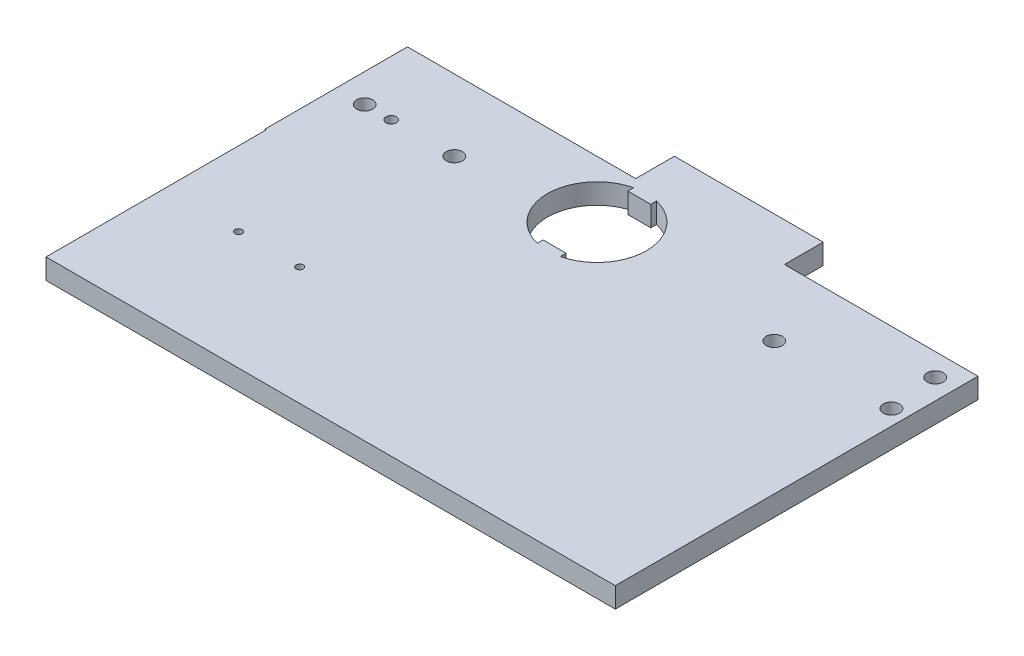
SolidWorks part; units mm, degrees
ref_plane "Front Plane" through (0, 0, 0) normal (0, 0, 1) x (1, 0, 0)
ref_plane "Top Plane" through (0, 0, 0) normal (0, 1, 0) x (1, 0, 0)
ref_plane "Right Plane" through (0, 0, 0) normal (1, 0, 0) x (0, 0, -1)
sketch "Sketch1" plane through (0, 0, 0) normal (0, 1, 0) x (1, 0, 0)
  line L1 (0, 0) -> (280, 0)
  line L2 (0, 0) -> (0, 70)
  line L3 (0, 70) -> (280, 70)
  line L4 (280, 0) -> (280, 70)
  circle A0 centre (14, 35) radius 3.9688
  circle A1 centre (58, 35) radius 3.9688
  circle A2 centre (215, 35) radius 3.9687
  circle A3 centre (272.5, 35) radius 3.9687
  circle A5 centre (270, 59) radius 3.9688
  circle A6 centre (58, 35) radius 27.5336
  circle A7 centre (215, 35) radius 27.5336
  circle A8 centre (27, 35) radius 2.55
  circle A9 centre (215, 35) radius 50.34
  point P20 (0, 0)
  dimension "D3" = 7.9375
  dimension "D6" = 58
  dimension "D7" = 7.9375
  dimension "D9" = 7.9375
  dimension "D12" = 7.5
  dimension "D13" = 7.9375
  dimension "D15" = 7.9375
  dimension "D18" = 55.0672
  dimension "D19" = 55.0672
  dimension "D20" = 5.1
  dimension "D23" = 100.68
  dimension "D1" = 280
  dimension "D2" = 70
  dimension "D4" = 35
  dimension "D5" = 14
  dimension "D8" = 35
  dimension "D10" = 215
  dimension "D11" = 35
  dimension "D14" = 35
  dimension "D16" = 11
  dimension "D17" = 10
  dimension "D21" = 35
  dimension "D22" = 31
extrude "Boss-Extrude7" add sketch "Sketch1" along normal blind 10 contours A9 L3 L2 L1 A8 A6 A0 | A9 L1 L4 L3 A3 A5 | A7 A2 | L1 A9 L3 A7 | A6 A1 region at (91.8345, 0, -35) region at (165.8862, 0, -35) region at (262.3681, 0, -15.8385) region at (31.2452, 0, -35) region at (188.2452, 0, -35)
sketch "Sketch2" plane through (0, 0, 0) normal (0, 0, 1) x (1, 0, 0)
  line L0 (38.5, 0) -> (-38.5, 0) construction
  line L1 (0.6, 0) -> (280, 0)
  line L2 (0.6, 0) -> (0.6, 10)
  line L3 (0.6, 10) -> (280, 10)
  line L4 (280, 0) -> (280, 10)
  line L5 (280, 10) -> (280, 0) construction
  line L6 (0, 10) -> (280, 10) construction
  dimension "D1" = 279.4
extrude "Boss-Extrude8" add sketch "Sketch2" along normal blind 108 contours L2 L1 L4 L3
sketch "Sketch3" plane through (0, 10, 0) normal (0, 1, 0) x (1, 0, 0)
  line L0 (0, 70) -> (280, 70) construction
  line L1 (0.6, -108) -> (0.6, 0) construction
  line L2 (0, 11.56) -> (280, 11.56)
  line L3 (280, -108) -> (280, 70) construction
  line L4 (10.6, 4) -> (93.6, 4)
  line L5 (10.6, 4) -> (10.6, -104)
  line L6 (10.6, -104) -> (93.6, -104)
  line L7 (93.6, 4) -> (93.6, -104)
  line L8 (0.6, -108) -> (280, -108) construction
  line L9 (0, -5.5) -> (0, 5.5) construction
  line L10 (115.3607, 67.852) -> (126.6393, 67.852)
  line L11 (115.3607, 67.852) -> (115.3607, 62.78)
  line L12 (115.3607, 62.78) -> (126.6393, 62.78)
  line L13 (126.6393, 67.852) -> (126.6393, 62.78)
  line L14 (115.3607, 21.22) -> (126.6393, 21.22)
  line L15 (115.3607, 21.22) -> (115.3607, 16.148)
  line L16 (115.3607, 16.148) -> (126.6393, 16.148)
  line L17 (126.6393, 21.22) -> (126.6393, 16.148)
  line L18 (215, 35) -> (215, 4)
  circle A0 centre (215, 35) radius 23.44
  circle A1 centre (215, 35) radius 27.47
  circle A3 centre (215, 35) radius 50
  circle A4 centre (121, 42) radius 24.28
  circle A5 centre (58, 35) radius 27.47
  circle A7 centre (37.1, -50) radius 1.7526
  circle A8 centre (67.1, -50) radius 1.7526
  point P19 (10.6, -50)
  point P20 (52.1, -104)
  point P27 (121, 62.78)
  point P34 (121, 16.148)
  point P35 (121, 21.22)
  point P44 (93.6, -50)
  dimension "D1" = 46.88
  dimension "D2" = 54.94
  dimension "D4" = 100
  dimension "D5" = 28
  dimension "D7" = 48.56
  dimension "D21" = 54.94
  dimension "D22" = 3.5052
  dimension "D25" = 3.5052
  dimension "D3" = 280
  dimension "D6" = 94
  dimension "D8" = 108
  dimension "D9" = 83
  dimension "D10" = 10
  dimension "D11" = 4
  dimension "D12" = 5.072
  dimension "D13" = 20.78
  dimension "D14" = 11.2786
  dimension "D15" = 121
  dimension "D16" = 20.78
  dimension "D17" = 5.6393
  dimension "D18" = 5.072
  dimension "D19" = 11.2786
  dimension "D20" = 121
  dimension "D23" = 54
  dimension "D24" = 26.5
  dimension "D26" = 54
  dimension "D27" = 26.5
extrude "Cut-Extrude2" cut sketch "Sketch3" against normal through all contours L17 A4 L13 L12 L11 L15 L14 region at (121, 10, -42)
extrude "Cut-Extrude3" cut sketch "Sketch3<7>" against normal blind 35 contours A7 region at (37.1, 10, 50)
sketch "Sketch3<7>" plane through (0, 10, 0) normal (0, 1, 0) x (1, 0, 0) same geometry as "Sketch3"
extrude "Cut-Extrude4" cut sketch "Sketch3<8>" against normal blind 32 contours A8 region at (67.1, 10, 50)
sketch "Sketch3<8>" plane through (0, 10, 0) normal (0, 1, 0) x (1, 0, 0) same geometry as "Sketch3"
sketch "Sketch4" plane through (0, 0, 0) normal (0, 0, 1) x (1, 0, 0)
extrude "Boss-Extrude9" add sketch "Sketch2<3>" along normal blind 10
sketch "Sketch2<3>" plane through (0, 0, 0) normal (0, 0, 1) x (1, 0, 0) same geometry as "Sketch2"
sketch "Sketch10" plane through (0, 0, -70) normal (0, 0, -1) x (-1, 0, 0)
  line L0 (0, 10) -> (-280, 10) construction
  line L1 (-185, 10) -> (-112, 10)
  line L2 (-185, 10) -> (-185, 0)
  line L3 (-185, 0) -> (-112, 0)
  line L4 (-112, 10) -> (-112, 0)
  line L5 (97.9, 0) -> (-97.9, 0) construction
  line L6 (-280, 10) -> (-280, 0) construction
  point P8 (-185, 5)
  point P11 (-280, 5)
  dimension "D1" = 95
  dimension "D2" = 73
extrude "Boss-Extrude11" add sketch "Sketch10" along normal blind 19
